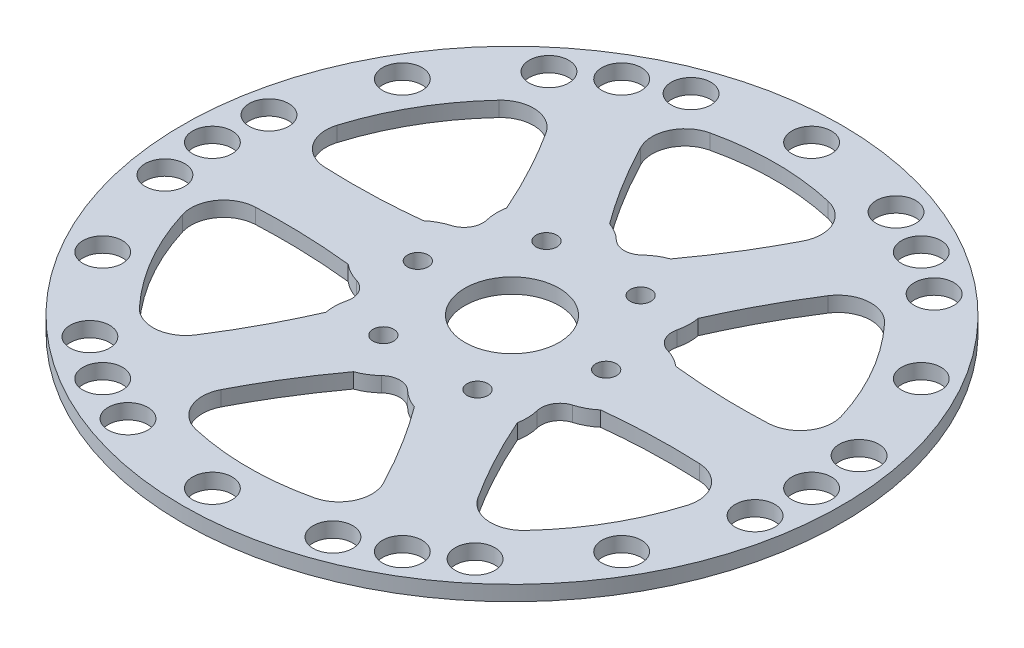
SolidWorks part; units mm, degrees
ref_plane "Front Plane" through (0, 0, 0) normal (0, 0, 1) x (1, 0, 0)
ref_plane "Top Plane" through (0, 0, 0) normal (0, 1, 0) x (1, 0, 0)
ref_plane "Right Plane" through (0, 0, 0) normal (1, 0, 0) x (0, 0, -1)
sketch "Sketch1" plane through (0, 0, 0) normal (0, 1, 0) x (1, 0, 0)
  line L0 (0, 0) -> (-28, 0) construction
  line L1 (0, 4) -> (-27.7128, 4)
  line L2 (0, -4) -> (-27.7128, -4)
  line L3 (-28, 0) -> (-31.8198, 0) construction
  line L4 (3.4641, 2) -> (-10.3923, 26)
  line L5 (-3.4641, -2) -> (-17.3205, 22)
  line L6 (3.4641, -2) -> (17.3205, 22)
  line L7 (-3.4641, 2) -> (10.3923, 26)
  line L8 (0, -4) -> (27.7128, -4)
  line L9 (0, 4) -> (27.7128, 4)
  line L10 (-3.4641, -2) -> (10.3923, -26)
  line L11 (3.4641, 2) -> (17.3205, -22)
  line L12 (-3.4641, 2) -> (-17.3205, -22)
  line L13 (3.4641, -2) -> (-10.3923, -26)
  line L14 (0, 4) -> (-28, 4) construction
  line L15 (0, -4) -> (-28, -4) construction
  circle A0 centre (0, 0) radius 31.8198 construction
  circle A1 centre (0, 0) radius 35
  circle A2 centre (0, 0) radius 28
  circle A3 centre (-31.8198, 0) radius 2.1
  circle A4 centre (0, 0) radius 5
  circle A6 centre (-15.9099, 27.5568) radius 2.1
  circle A8 centre (15.9099, 27.5568) radius 1.1
  circle A10 centre (31.8198, 0) radius 1.1
  circle A12 centre (15.9099, -27.5568) radius 1.1
  circle A14 centre (-15.9099, -27.5568) radius 1.1
  circle A15 centre (0, 31.8198) radius 2.1
  circle A16 centre (15.9099, 27.5568) radius 2.1
  circle A17 centre (27.5568, 15.9099) radius 2.1
  circle A18 centre (31.8198, 0) radius 2.1
  circle A19 centre (27.5568, -15.9099) radius 2.1
  circle A20 centre (15.9099, -27.5568) radius 2.1
  circle A21 centre (0, -31.8198) radius 2.1
  circle A22 centre (-15.9099, -27.5568) radius 2.1
  circle A23 centre (-27.5568, -15.9099) radius 2.1
  circle A24 centre (-31.8198, 0) radius 2.1
  circle A25 centre (-27.5568, 15.9099) radius 2.1
  circle A26 centre (-20.4534, 24.3754) radius 2.1
  circle A27 centre (-10.883, 29.9008) radius 2.1
  circle A28 centre (10.883, 29.9008) radius 2.1
  circle A29 centre (31.3364, 5.5255) radius 2.1
  circle A30 centre (20.4534, -24.3754) radius 2.1
  circle A31 centre (-10.883, -29.9008) radius 2.1
  circle A32 centre (-31.3364, -5.5255) radius 2.1
  circle A33 centre (20.4534, 24.3754) radius 2.1
  circle A34 centre (31.3364, -5.5255) radius 2.1
  circle A35 centre (10.883, -29.9008) radius 2.1
  circle A36 centre (-20.4534, -24.3754) radius 2.1
  circle A37 centre (-31.3364, 5.5255) radius 2.1
  point P44 (0, 0)
  point P45 (0, 0)
  point P68 (0, 0)
  point P71 (0, 0)
  point P74 (0, 0)
  point P85 (0, 0)
  point P96 (0, 0)
  dimension "D1" = 63.6396
  dimension "D2" = 4
  dimension "D3" = 70
  dimension "D5" = 12
  dimension "D10" = 6
  dimension "D4" = 4
  dimension "D6" = 2
  dimension "D7" = 2
  dimension "D8" = 6
  dimension "D9" = 6
extrude "Boss-Extrude1" add sketch "Sketch1" along normal blind 1.6 contours A1 A37 A36 A35 A34 A33 A32 A31 A30 A29 A28 A27 A26 A25 A23 A21 A19 A17 A15 A14 A12 A10 A8 A6 A3 A2 | L1 A2 L2 L12 L5 | L4 A2 L5 L1 L7 | L6 A2 L7 L4 L9 | L8 A2 L9 L6 L11 | L10 A2 L11 L8 L13 | L12 A2 L13 L10 L2 | A4 L1 L5 | A4 L12 L2 | A4 L10 L13 | A4 L8 L11 | A4 L6 L9 | A4 L4 L7 region at (-5.1232, 0, -2.9579) region at (-8.4225, 0, -14.5882) region at (0, 0, -5.9157) region at (8.4225, 0, -14.5882) region at (5.1232, 0, -2.9579) region at (-16.845, 0, 0) region at (16.845, 0, 0) region at (-5.1232, 0, 2.9579) region at (5.1232, 0, 2.9579) region at (-8.4225, 0, 14.5882) region at (8.4225, 0, 14.5882) region at (0, 0, 5.9157) region at (-34.0101, 0, 0)
sketch "Sketch3" plane through (0, 1.6, 0) normal (0, 1, 0) x (1, 0, 0)
  line L0 (0, 0) -> (-11.3813, 0) construction
  circle A0 centre (0, 0) radius 10 construction
  circle A1 centre (-10, 0) radius 1.1
  circle A2 centre (-10, 0) radius 5.25
  circle A3 centre (-5, 8.6603) radius 5.25
  circle A4 centre (5, 8.6603) radius 5.25
  circle A5 centre (10, 0) radius 5.25
  circle A6 centre (5, -8.6603) radius 5.25
  circle A7 centre (-5, -8.6603) radius 5.25
  circle A8 centre (-5, 8.6603) radius 1.1
  circle A9 centre (5, 8.6603) radius 1.1
  circle A10 centre (10, 0) radius 1.1
  circle A11 centre (5, -8.6603) radius 1.1
  circle A12 centre (-5, -8.6603) radius 1.1
  point P19 (0, 0)
  point P30 (0, 0)
  line M86 (-10.3923, -26) -> (0, -8)
  line M87 (0, -8) -> (10.3923, -26)
  line M88 (-27.7128, -4) -> (-6.9282, -4)
  line M89 (-6.9282, -4) -> (-17.3205, -22)
  line M90 (-17.3205, 22) -> (-6.9282, 4)
  line M91 (-6.9282, 4) -> (-27.7128, 4)
  line M92 (10.3923, 26) -> (0, 8)
  line M93 (0, 8) -> (-10.3923, 26)
  line M94 (27.7128, 4) -> (6.9282, 4)
  line M95 (6.9282, 4) -> (17.3205, 22)
  line M96 (17.3205, -22) -> (6.9282, -4)
  line M97 (6.9282, -4) -> (27.7128, -4)
  dimension "D1" = 6
  dimension "D2" = 6
extrude "Boss-Extrude2" add sketch "Sketch3" against normal blind 1.6 contours A3 A2 M91 | A3 A2 M90 | A4 A3 M93 | A4 A3 M92 | A5 A4 M95 | A5 A4 M94 | A6 A5 M97 | A6 A5 M96 | A7 A6 M87 | A7 A6 M86 | A2 A7 M89 | A7 A2 M88 | A2 A3 M91 M90 | A3 A4 M93 M92 | A4 A5 M95 M94 | A5 A6 M97 M96 | A6 A7 M87 M86 | A7 A2 M88 M89 region at (-7.8087, 1.6, -4.5083) region at (-9.0961, 1.6, -6.7339) region at (-10.3798, 1.6, -4.5105) region at (-9.0961, 1.6, 6.7339) region at (-7.8087, 1.6, 4.5083) region at (-10.3798, 1.6, 4.5105) region at (0, 1.6, -9.0167) region at (1.2837, 1.6, -11.2444) region at (-1.2837, 1.6, -11.2444) region at (0, 1.6, 9.0167) region at (-1.2837, 1.6, 11.2444) region at (1.2837, 1.6, 11.2444) region at (7.8087, 1.6, -4.5083) region at (10.3798, 1.6, -4.5105) region at (9.0961, 1.6, -6.7339) region at (7.8087, 1.6, 4.5083) region at (9.0961, 1.6, 6.7339) region at (10.3798, 1.6, 4.5105)
sketch "Sketch4" plane through (0, 1.6, 0) normal (0, 1, 0) x (1, 0, 0)
  circle A0 centre (0, 0) radius 10 construction
  circle A1 centre (-10, 0) radius 1.1
  circle A2 centre (-5, 8.6603) radius 1.1
  circle A3 centre (5, 8.6603) radius 1.1
  circle A4 centre (10, 0) radius 1.1
  circle A5 centre (5, -8.6603) radius 1.1
  circle A6 centre (-5, -8.6603) radius 1.1
  point P17 (0, 0)
  dimension "D1" = 6
extrude "Cut-Extrude1" cut sketch "Sketch4" against normal through all
sketch "Sketch5" plane through (0, 1.6, 0) normal (0, 1, 0) x (1, 0, 0)
  line L0 (-17.3205, 22) -> (-27.7128, 4)
  line L1 (-13.4004, 4) -> (-10.1643, 9.6051)
  line L2 (-3.2361, 13.6051) -> (3.2361, 13.6051)
  line L3 (10.3923, 26) -> (-10.3923, 26)
  line L4 (10.1643, 9.6051) -> (13.4004, 4)
  line L5 (27.7128, 4) -> (17.3205, 22)
  line L6 (13.4004, -4) -> (10.1643, -9.6051)
  line L7 (17.3205, -22) -> (27.7128, -4)
  line L8 (3.2361, -13.6051) -> (-3.2361, -13.6051)
  line L9 (-10.3923, -26) -> (10.3923, -26)
  line L10 (-10.1643, -9.6051) -> (-13.4004, -4)
  line L11 (-27.7128, -4) -> (-17.3205, -22)
  spline S0 degree 2 poles (-27.7128, 4) (-20.5568, 3.2185) (-13.4004, 4) knots 0 0 0 1 1 1
  spline S1 degree 2 poles (-17.3205, 22) (-13.0583, 16.1975) (-10.1643, 9.6051) knots 0 0 0 1 1 1
  spline S2 degree 2 poles (10.3923, 26) (7.4983, 19.4076) (3.2361, 13.6051) knots 0 0 0 1 1 1
  spline S3 degree 2 poles (-10.3923, 26) (-7.4911, 19.412) (-3.2361, 13.6051) knots 0 0 0 1 1 1
  spline S4 degree 2 poles (27.7128, 4) (20.5566, 3.2101) (13.4004, 4) knots 0 0 0 1 1 1
  spline S5 degree 2 poles (17.3205, 22) (13.0657, 16.1935) (10.1643, 9.6051) knots 0 0 0 1 1 1
  spline S6 degree 2 poles (17.3205, -22) (13.0583, -16.1975) (10.1643, -9.6051) knots 0 0 0 1 1 1
  spline S7 degree 2 poles (27.7128, -4) (20.5568, -3.2185) (13.4004, -4) knots 0 0 0 1 1 1
  spline S8 degree 2 poles (-10.3923, -26) (-7.4983, -19.4076) (-3.2361, -13.6051) knots 0 0 0 1 1 1
  spline S9 degree 2 poles (10.3923, -26) (7.4911, -19.412) (3.2361, -13.6051) knots 0 0 0 1 1 1
  spline S10 degree 2 poles (-27.7128, -4) (-20.5566, -3.2101) (-13.4004, -4) knots 0 0 0 1 1 1
  spline S11 degree 2 poles (-17.3205, -22) (-13.0657, -16.1935) (-10.1643, -9.6051) knots 0 0 0 1 1 1
  point P42 (0, 0)
  dimension "D1" = 6
extrude "Cut-Extrude2" cut sketch "Sketch5" against normal through all
fillet "Fillet2" radius 2 1 edges at (0, 0.8, -10.261)
fillet "Fillet3" radius 2 1 edges at (-8.8863, 0.8, -5.1305)
fillet "Fillet4" radius 2 1 edges at (8.8863, 0.8, -5.1305)
fillet "Fillet5" radius 2 1 edges at (8.8863, 0.8, 5.1305)
fillet "Fillet6" radius 2 1 edges at (0, 0.8, 10.261)
fillet "Fillet7" radius 2 1 edges at (-8.8863, 0.8, 5.1305)
fillet "Fillet8" radius 3.5 12 edges at (17.3205, 0.8, -22) (27.7128, 0.8, -4) (27.7128, 0.8, 4) (17.3205, 0.8, 22) (10.3923, 0.8, 26) (-10.3923, 0.8, 26) (-17.3205, 0.8, 22) (-27.7128, 0.8, 4) (-27.7128, 0.8, -4) (-17.3205, 0.8, -22) (10.3923, 0.8, -26) (-10.3923, 0.8, -26)
